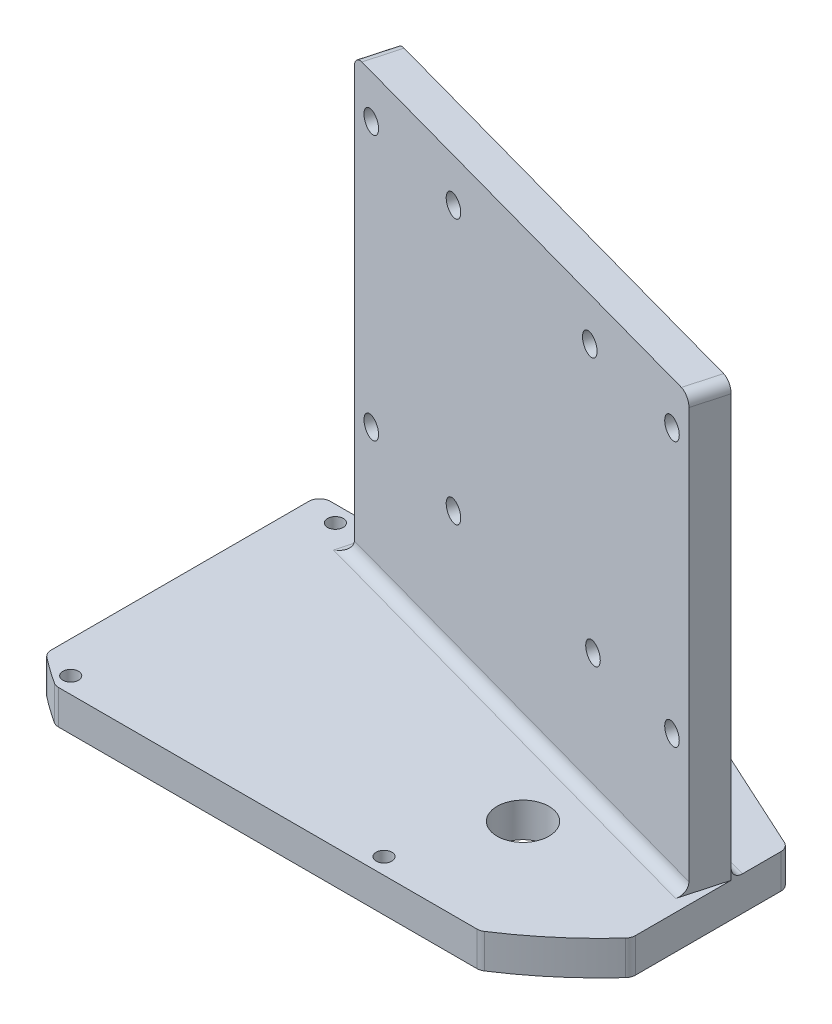
SolidWorks part; units mm, degrees
ref_plane "Front Plane" through (0, 0, 0) normal (0, 0, 1) x (1, 0, 0)
ref_plane "Top Plane" through (0, 0, 0) normal (0, 1, 0) x (1, 0, 0)
ref_plane "Right Plane" through (0, 0, 0) normal (1, 0, 0) x (0, 0, -1)
sketch "Sketch1" plane through (0, 0, 0) normal (0, 1, 0) x (1, 0, 0)
  line L1 (-34.925, -27.5) -> (34.925, -27.5)
  line L2 (-34.925, -27.5) -> (-34.925, 27.5)
  line L3 (-34.925, 27.5) -> (34.925, 27.5)
  line L4 (34.925, -27.5) -> (34.925, 27.5)
  line L5 (-34.925, -27.5) -> (34.925, 27.5) construction
  line L6 (-34.925, 27.5) -> (34.925, -27.5) construction
  point P0 (0, 0)
  dimension "D1" = 55
  dimension "D2" = 69.85
extrude "Boss-Extrude1" add sketch "Sketch1" along normal blind 6.35
sketch "Sketch10" plane through (34.925, 0, 0) normal (1, 0, 0) x (0, 0, -1)
  line L12 (-27.5, 0) -> (27.5, 0)
  line L13 (27.5, 0) -> (27.5, 6.35)
  line L14 (27.5, 6.35) -> (-27.5, 6.35)
  line L19 (-27.5, 6.35) -> (-27.5, 0)
  line L20 (-27.5, 0) -> (27.5, 0)
  line L21 (27.5, 0) -> (27.5, 6.35)
  line L22 (27.5, 6.35) -> (-27.5, 6.35)
  line L27 (-27.5, 6.35) -> (-27.5, 0)
  dimension "D1" = 0
extrude "Boss-Extrude3" add sketch "Sketch10" along normal blind 30
sketch "Sketch2" plane through (0, 6.35, 0) normal (0, 1, 0) x (1, 0, 0)
  line L0 (64.925, 27.5) -> (-34.925, 27.5) construction
  line L1 (-20.6823, 27.5) -> (64.925, 3.8361)
  line L2 (-20.6823, 27.5) -> (-22.3741, 21.3795)
  line L3 (-22.3741, 21.3795) -> (63.2332, -2.2843)
  line L4 (64.925, 3.8361) -> (63.2332, -2.2843)
  line L6 (64.925, 27.5) -> (64.925, -27.5) construction
  point P4 (0, 0)
  point P5 (0, 0)
  point P6 (0, 0)
  point P7 (0, 0)
  point P8 (0, 0)
  point P10 (0, 0)
  point P11 (0, 0)
  point P12 (0, 0)
  point P14 (0, 0)
  point P15 (31.195, 1.5273)
  point P16 (0, 0)
  point P17 (0, 0)
  point P19 (0, 0)
  point P21 (-20.6823, 27.5)
  point P22 (64.925, 1.7625)
  point P23 (64.925, 3.8361)
  dimension "D1" = 6.35
extrude "Boss-Extrude2" add sketch "Sketch2" along normal blind 80
sketch "Sketch7" plane through (0, 0, 0) normal (0, -1, 0) x (1, 0, 0)
  line L0 (-34.925, 27.5) -> (64.925, 27.5) construction
  line L1 (-14, 24.5) -> (44, 24.5)
  line L2 (-14, 24.5) -> (-14, -24.5)
  line L3 (-14, -24.5) -> (44, -24.5)
  line L4 (44, 24.5) -> (44, -24.5)
  point P4 (15, 27.5)
  point P7 (15, 24.5)
  dimension "D1" = 58
  dimension "D2" = 49
  dimension "D3" = 3
hole_wizard "M2.5 Clearance Hole1" positions "Sketch8" profile "Sketch9" hole size "M2.5" standard "ANSI Metric" end condition through all
sketch "Sketch8" plane through (0, 0, 0) normal (0, -1, 0) x (-1, 0, 0)
  line L0 (34.925, 27.5) -> (34.925, -27.5) construction
  line L1 (34.925, -27.5) -> (-64.925, -27.5) construction
  point P17 (28.995, 24.5)
  point P19 (-29.005, 24.5)
  point P21 (-29.005, -24.5)
  point P23 (28.995, -24.5)
  dimension "D1" = 5.93
  dimension "D2" = 3
  dimension "D3" = 49
  dimension "D4" = 58
sketch "Sketch9" plane through (-28.995, 0, -24.5) normal (1, 0, 0) x (0, 0, -1)
  line L0 (0, 0) -> (0, 86.35)
  line L1 (0, 86.35) -> (1.45, 86.35)
  line L2 (1.45, 86.35) -> (1.45, 0)
  line L5 (1.45, 0) -> (0, 0)
  line L11 (0, -6.35) -> (0, 107.95) construction
  dimension "Thru Hole Dia." = 2.9
  dimension "Thru Hole Depth" = 86.35
hole_wizard "#24 (0.152) Diameter Hole1" positions "Sketch4" profile "Sketch5" hole size "#24" standard "ANSI Inch" end condition through all
sketch "Sketch4" plane through (3.902, 0, -14.1162) normal (-0.2664, 0, 0.9639) x (0.9639, 0, 0.2664)
  line L0 (-0.9439, 78.35) -> (57.0561, 78.35) construction
  line L2 (57.0561, 78.35) -> (57.0561, 29.35) construction
  line L3 (-27.2615, 86.35) -> (61.5561, 86.35) construction
  line L4 (61.5561, 86.35) -> (61.5561, 6.35) construction
  line L5 (-27.2615, 86.35) -> (-27.2615, 6.35) construction
  point P19 (-0.9439, 78.35)
  point P21 (57.0561, 78.35)
  point P23 (-0.9439, 29.35)
  point P25 (57.0561, 29.35)
  point P44 (-22.7615, 78.35)
  point P46 (35.2385, 78.35)
  point P48 (36.0889, 29.3574)
  point P50 (-22.7615, 29.3574)
  point P53 (0, 0)
  point P54 (0, 0)
  dimension "D1" = 58
  dimension "D2" = 49
  dimension "D3" = 8
  dimension "D4" = 4.5
  dimension "D5" = 58
  dimension "D6" = 49
  dimension "D7" = 8
  dimension "D8" = 4.5
sketch "Sketch5" plane through (2.9923, 78.35, -14.3677) normal (0, 1, 0) x (0.9639, 0, 0.2664)
  line L0 (0, 0) -> (0, 29.1585)
  line L1 (0, 29.1585) -> (1.9304, 29.1585)
  line L2 (1.9304, 29.1585) -> (1.9304, 0)
  line L5 (1.9304, 0) -> (0, 0)
  line L11 (0, -6.35) -> (0, 107.95) construction
  dimension "Thru Hole Dia." = 3.8608
  dimension "Thru Hole Depth" = 29.1585
sketch "Sketch11" plane through (0, 6.35, 0) normal (0, 1, 0) x (1, 0, 0)
  line L2 (64.925, 3.8361) -> (64.925, -27.5) construction
  line L3 (-34.925, 27.5) -> (-34.925, -27.5) construction
  line L4 (-34.925, -27.5) -> (64.925, -27.5) construction
  line L5 (49.7882, -27.5) -> (64.925, -27.5)
  line L7 (64.925, -14.6211) -> (64.925, -27.5)
  line L8 (-34.925, -23.1569) -> (-34.925, -27.5)
  line L9 (-34.925, -27.5) -> (-28.8375, -27.5)
  line L11 (64.925, 27.5) -> (-20.6823, 27.5) construction
  line L12 (-1.8842, 27.5) -> (-1.8842, 22.3038)
  line L13 (64.925, 27.5) -> (64.7963, 27.5)
  line L14 (64.925, 3.8361) -> (-20.6823, 27.5) construction
  line L15 (-1.8842, 22.3038) -> (4.7524, 20.4693)
  line L16 (23.0045, 20.4693) -> (23.0045, 27.5)
  line L17 (23.0045, 27.5) -> (-1.8842, 27.5)
  line L18 (36.1925, 27.5) -> (64.925, 27.5)
  line L19 (4.7524, 20.4693) -> (23.0045, 20.4693)
  line L20 (36.1925, 27.5) -> (64.925, 14.3127)
  line L21 (64.925, 27.5) -> (64.925, 3.8361) construction
  line L22 (64.925, 27.5) -> (64.925, 14.3127)
  line L23 (64.925, 3.8361) -> (-20.6823, 27.5) construction
  circle A2 centre (10.4754, 34.0398) radius 73.025 construction
  arc A3 (-34.925, -23.1569) -> (-28.8375, -27.5) centre (10.4754, 34.0398) ccw
  arc A4 (49.7882, -27.5) -> (64.925, -14.6211) centre (10.4754, 34.0398) ccw
  circle A10 centre (36.1925, -5.9602) radius 4.8
  circle A11 centre (36.1925, -5.9602) radius 4.8
  line M7 (-34.925, 27.5) -> (-34.925, -27.5)
  line M8 (-34.925, -27.5) -> (64.925, -27.5)
  line M9 (64.925, -27.5) -> (64.925, 3.8361)
  dimension "D1" = 3
extrude "Cut-Extrude1" cut sketch "Sketch11" against normal up to next contours L13 | A4 M8 M9 | A3 M7 M8 | L17 L12 L15 L19 L16 | A11 | L18 L20 L22 region at (60.1184, 6.35, 23.4045) region at (-32.933, 6.35, 26.0782) region at (55.3475, 6.35, -23.1042)
fillet "Fillet1" radius 2 17 edges at (-28.8375, 3.175, 27.5) (-34.925, 3.175, 23.1569) (64.925, 3.175, 14.6211) (49.7882, 3.175, 27.5) (36.1925, 3.175, -27.5) (64.925, 3.175, -14.3127) (23.0045, 3.175, -27.5) (23.0045, 3.175, -20.4693) (-1.8842, 3.175, -27.5) (-34.925, 3.175, -27.5) (4.7524, 3.175, -20.4693) (-1.8842, 3.175, -22.3038) (-21.5282, 86.35, -24.4398) (64.0791, 86.35, -0.7759) (-21.5282, 6.35, -24.4398) (20.4295, 6.35, -9.5476) (34.8387, 6.35, -12.1527)
